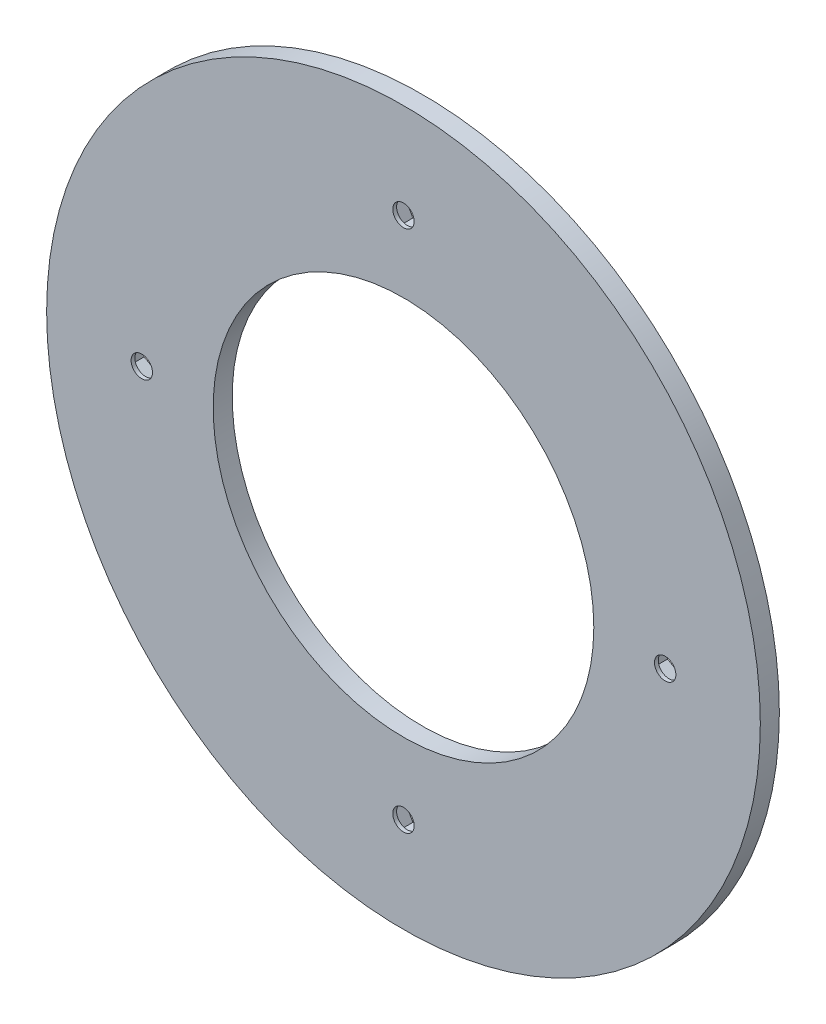
SolidWorks part; units mm, degrees
material "PET"
ref_plane "Front Plane" through (0, 0, 0) normal (0, 0, 1) x (1, 0, 0)
ref_plane "Top Plane" through (0, 0, 0) normal (0, 1, 0) x (1, 0, 0)
ref_plane "Right Plane" through (0, 0, 0) normal (1, 0, 0) x (0, 0, -1)
sketch "Sketch1" plane through (0, 0, 0) normal (0, 0, 1) x (1, 0, 0)
  circle A0 centre (0, 0) radius 75
  circle A1 centre (0, 0) radius 40
  dimension "D1" = 150
  dimension "D2" = 35
extrude "Boss-Extrude1" add sketch "Sketch1" along normal blind 4
sketch "Sketch2" plane through (0, 0, 4) normal (0, 0, 1) x (1, 0, 0)
  circle A0 centre (0, 0) radius 73
  circle A1 centre (0, 0) radius 75
  circle A2 centre (0, 0) radius 75
  dimension "D1" = 0
  dimension "D2" = 2
extrude "Boss-Extrude2" [suppressed] add sketch "Sketch2" along normal blind 8
sketch "Sketch3" [suppressed] plane through (0, 0, 0) normal (0, 1, 0) x (1, 0, 0)
  line L0 (-75, -12) -> (75, -12) construction
  circle A0 centre (0, -7) radius 1.5
  dimension "D2" = 3
  dimension "D1" = 5
extrude "Cut-Extrude1" [suppressed] cut sketch "Sketch3" against normal up to surface (75 mm away) up to face at (75, 0, 4)
pattern_circular "CirPattern1" [suppressed] count 4 over 360 of bodies 103
sketch "Sketch9" plane through (0, 0, 0) normal (0, 0, -1) x (-1, 0, 0)
  point P0 (0, 55)
  point P4 (55, 0)
  point P6 (0, -55)
  point P8 (-55, 0)
  dimension "D1" = 55
  dimension "D2" = 0
  dimension "D3" = 55
  dimension "D4" = 55
  dimension "D5" = 55
hole_wizard "M4 Clearance Hole1" positions "Sketch9" profile "Sketch10" hole size "M4" standard "ISO" end condition through all
sketch "Sketch10" plane through (0, 55, 0) normal (1, 0, 0) x (0, 1, 0)
  line L0 (0, 0) -> (0, 4)
  line L1 (0, 4) -> (2.25, 4)
  line L2 (2.25, 4) -> (2.25, 0)
  line L5 (2.25, 0) -> (0, 0)
  line L11 (0, -6.35) -> (0, 107.95) construction
  dimension "Thru Hole Dia." = 4.5
  dimension "Thru Hole Depth" = 4
sketch "Sketch13" plane through (0, 0, 0) normal (0, 0, -1) x (-1, 0, 0)
  line L0 (0, 0) -> (55, 0) construction
  line L1 (4.0415, 55) -> (2.0207, 58.5)
  line L2 (2.0207, 58.5) -> (-2.0207, 58.5)
  line L3 (-2.0207, 58.5) -> (-4.0415, 55)
  line L4 (-4.0415, 55) -> (-2.0207, 51.5)
  line L5 (-2.0207, 51.5) -> (2.0207, 51.5)
  line L6 (2.0207, 51.5) -> (4.0415, 55)
  line L7 (55, -4.0415) -> (58.5, -2.0207)
  line L8 (58.5, -2.0207) -> (58.5, 2.0207)
  line L9 (58.5, 2.0207) -> (55, 4.0415)
  line L10 (55, 4.0415) -> (51.5, 2.0207)
  line L11 (51.5, 2.0207) -> (51.5, -2.0207)
  line L12 (51.5, -2.0207) -> (55, -4.0415)
  line L13 (-4.0415, -55) -> (-2.0207, -58.5)
  line L14 (-2.0207, -58.5) -> (2.0207, -58.5)
  line L15 (2.0207, -58.5) -> (4.0415, -55)
  line L16 (4.0415, -55) -> (2.0207, -51.5)
  line L17 (2.0207, -51.5) -> (-2.0207, -51.5)
  line L18 (-2.0207, -51.5) -> (-4.0415, -55)
  line L19 (-55, 4.0415) -> (-58.5, 2.0207)
  line L20 (-58.5, 2.0207) -> (-58.5, -2.0207)
  line L21 (-58.5, -2.0207) -> (-55, -4.0415)
  line L22 (-55, -4.0415) -> (-51.5, -2.0207)
  line L23 (-51.5, -2.0207) -> (-51.5, 2.0207)
  line L24 (-51.5, 2.0207) -> (-55, 4.0415)
  circle A0 centre (0, 55) radius 3.5 construction
  circle A1 centre (55, 0) radius 3.5 construction
  circle A2 centre (0, -55) radius 3.5 construction
  circle A3 centre (-55, 0) radius 3.5 construction
  point P40 (0, 0)
  dimension "D1" = 7
extrude "Cut-Extrude2" cut sketch "Sketch13" against normal blind 3.2
